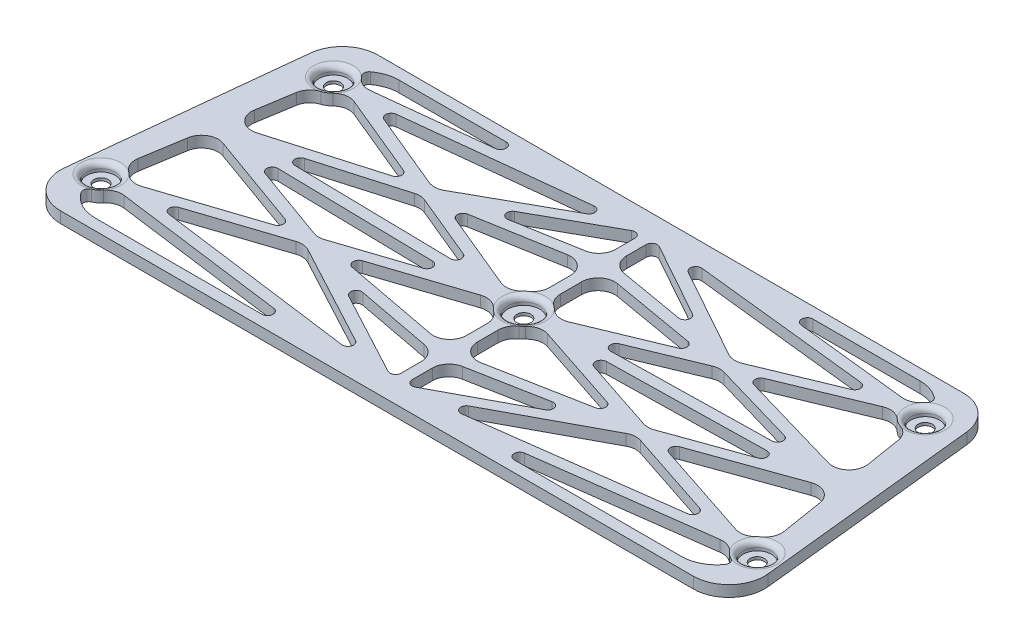
SolidWorks part; units mm, degrees
ref_plane "Front Plane" through (0, 0, 0) normal (0, 0, 1) x (1, 0, 0)
ref_plane "Top Plane" through (0, 0, 0) normal (0, 1, 0) x (1, 0, 0)
ref_plane "Right Plane" through (0, 0, 0) normal (1, 0, 0) x (0, 0, -1)
sketch "Sketch1" plane through (0, 0, 0) normal (0, 1, 0) x (1, 0, 0)
  line L0 (-101.6, -41.91) -> (-92.71, 41.91)
  line L1 (-101.6, -41.91) -> (101.6, -41.91)
  line L2 (-101.6, -41.91) -> (-101.6, 41.91)
  line L3 (-101.6, 41.91) -> (101.6, 41.91)
  line L4 (101.6, -41.91) -> (101.6, 41.91)
  line L5 (-101.6, -41.91) -> (101.6, 41.91) construction
  line L6 (-101.6, 41.91) -> (101.6, -41.91) construction
  line L7 (0, 41.91) -> (0, -41.91) construction
  line L8 (101.6, -41.91) -> (92.71, 41.91)
  circle A0 centre (0, 0) radius 2.032
  circle A1 centre (-93.6752, -27.0205) radius 2.032
  circle A2 centre (-84.4677, 30.1295) radius 2.032
  circle A3 centre (93.6752, -27.0205) radius 2.032
  circle A4 centre (84.4677, 30.1295) radius 2.032
  point P0 (0, 0)
  dimension "D1" = 4.064
  dimension "D6" = 4.064
  dimension "D2" = 203.2
  dimension "D3" = 83.82
  dimension "D4" = 8.89
  dimension "D5" = 83.946
  dimension "D7" = 14.8895
  dimension "D8" = 7.9248
  dimension "D9" = 57.15
  dimension "D10" = 9.2075
extrude "platw" add sketch "Sketch1" along normal blind 3.175 contours L1 L8 L3 L0 A3 A2 A1 A0 A4 region at (-94.9692, 0, 0.2318)
fillet "Fillet1" radius 10.16 2 edges at (101.6, 1.5875, 41.91) (-101.6, 1.5875, 41.91)
fillet "Fillet2" radius 10.16 2 edges at (-92.71, 1.5875, -41.91) (92.71, 1.5875, -41.91)
sketch "Sketch2" plane through (0, 3.175, 0) normal (0, 1, 0) x (1, 0, 0)
  circle A0 centre (-84.4677, 30.1295) radius 4.064
  circle A1 centre (-93.6752, -27.0205) radius 4.064
  circle A2 centre (93.6752, -27.0205) radius 4.064
  circle A3 centre (84.4677, 30.1295) radius 4.064
  circle A4 centre (0, 0) radius 4.572
  dimension "D1" = 8.128
  dimension "D2" = 9.144
extrude "countersinks" cut sketch "Sketch2" against normal blind 2.3813
sketch "Sketch3" plane through (0, 3.175, 0) normal (0, 1, 0) x (1, 0, 0)
  line L0 (-88.0237, -27.0205) -> (-6.1595, 0) construction
  line L1 (-47.0916, -13.5103) -> (-89.0714, 1.5545) construction
  line L2 (-88.0237, -27.0205) -> (0, -38.735) construction
  line L3 (-47.0916, -13.5103) -> (0, -22.4472) construction
  line L4 (-84.4677, 30.1295) -> (-93.6752, -27.0205)
  line L5 (-83.697, -38.735) -> (83.697, -38.735)
  line L6 (93.6752, -27.0205) -> (84.4677, 30.1295)
  line L7 (-74.3648, 38.735) -> (74.3648, 38.735)
  line L8 (-90.3054, -41.91) -> (90.3054, -41.91) construction
  line L9 (-83.5706, 41.91) -> (83.5706, 41.91) construction
  line L10 (-78.8162, 30.1295) -> (-6.1595, 0) construction
  line L11 (-47.0916, -13.5103) -> (0, -38.735) construction
  line L12 (-89.3283, -0.04) -> (-51.9664, -13.4475)
  line L13 (0, -38.735) -> (0, -6.1595)
  line L14 (0, 6.1595) -> (0, 38.735)
  line L15 (-78.8162, 30.1295) -> (0, 38.735) construction
  line L16 (0, 22.4473) -> (-42.4878, 15.0647) construction
  line L17 (-42.4878, 15.0647) -> (0, 38.735) construction
  line L18 (-6.1595, 0) -> (-89.0714, 1.5545) construction
  line L19 (-89.0714, 1.5545) -> (-42.4878, 15.0647) construction
  line L20 (-51.9664, -13.4475) -> (-88.2537, -25.4247)
  line L21 (-79.4439, -0.2138) -> (-47.07, -11.8314)
  line L22 (-47.07, -11.8314) -> (-15.5041, -1.4126)
  line L23 (-15.5041, -1.4126) -> (-79.4439, -0.2138)
  line L24 (-40.7674, -13.0946) -> (-5.9476, -1.6018)
  line L25 (-40.7674, -13.0946) -> (-1.5875, -20.5301)
  line L26 (-1.5875, -20.5301) -> (-1.5875, -5.9514)
  line L27 (-80.9563, -26.3596) -> (-8.4517, -36.0087)
  line L28 (-8.4517, -36.0087) -> (-47.2408, -15.2312)
  line L29 (-47.2408, -15.2312) -> (-80.9563, -26.3596)
  line L30 (-12.0338, -38.735) -> (-88.2467, -28.5923)
  line L31 (-37.213, -17.0008) -> (-1.5875, -36.0837)
  line L32 (-1.5875, -36.0837) -> (-1.5875, -23.7618)
  line L33 (-1.5875, -23.7618) -> (-37.213, -17.0008)
  line L34 (-79.0394, 31.702) -> (-14.626, 38.735)
  line L35 (-72.4873, 29.2236) -> (-7.6222, 36.3058)
  line L36 (-7.6222, 36.3058) -> (-42.5894, 16.8254)
  line L37 (-42.5894, 16.8254) -> (-72.4873, 29.2236)
  line L38 (-79.0534, 28.5093) -> (-47.2721, 15.3301)
  line L39 (-47.2721, 15.3301) -> (-88.7921, 3.2884)
  line L40 (-78.576, 2.9455) -> (-42.581, 13.3848)
  line L41 (-42.581, 13.3848) -> (-14.5103, 1.7443)
  line L42 (-14.5103, 1.7443) -> (-78.576, 2.9455)
  line L46 (0, 41.91) -> (0, -41.91) construction
  line L60 (-5.9405, 1.6278) -> (-36.829, 14.4367)
  line L61 (-36.829, 14.4367) -> (-1.5875, 20.5601)
  line L62 (-1.5875, 20.5601) -> (-1.5875, 5.9514)
  line L63 (-33.5443, 18.23) -> (-1.5875, 23.7827)
  line L64 (-1.5875, 23.7827) -> (-1.5875, 36.0334)
  line L65 (-1.5875, 36.0334) -> (-33.5443, 18.23)
  arc A0 (-79.0394, 31.702) -> (-82.063, 35.2439) centre (-84.4677, 30.1295) ccw
  arc A1 (-85.3666, 24.5499) -> (-79.0534, 28.5093) centre (-84.4677, 30.1295) ccw
  arc A4 (-84.4677, 30.1295) -> (-74.3648, 38.735) centre (-74.3648, 28.5018) cw
  arc A5 (74.3648, 38.735) -> (84.4677, 30.1295) centre (74.3648, 28.5018) cw
  arc A6 (-93.6752, -27.0205) -> (-83.697, -38.735) centre (-83.697, -28.6281) ccw
  arc A7 (83.697, -38.735) -> (93.6752, -27.0205) centre (83.697, -28.6281) ccw
  arc A9 (-92.7763, -21.441) -> (-88.2467, -28.5923) centre (-93.6752, -27.0205) cw
  arc A10 (-88.2467, -28.5923) -> (-92.9783, -32.6289) centre (-93.6752, -27.0205) cw
  circle A13 centre (0, 0) radius 6.1595
  point P73 (-1.5875, -13.2408)
  dimension "D3" = 12.319
  dimension "D4" = 5.6515
  dimension "D5" = 5.6515
  dimension "D1" = 3.175
  dimension "D2" = 3.175
extrude "pocket 1" cut sketch "Sketch3" against normal through all contours A4 L34 L7 | L37 L36 L35 | L64 L65 L63 | L42 L41 L40 | L39 L38 L4 | L62 L61 L60 | L22 L23 L21 | L20 L12 L4 | L28 L29 L27 | L32 L33 L31 | L25 L26 L24 | A6 L5 L30 region at (-73.0435, 3.175, -15.9243) region at (-58.1721, 3.175, -36.3358) region at (-77.871, 3.175, 13.1847) region at (-64.1002, 3.175, 35.2582) region at (-13.8195, 3.175, -12.03) region at (-15.1255, 3.175, 11.6139) region at (-47.3393, 3.175, 4.4859) region at (-45.5496, 3.175, 25.8665) region at (-13.4627, 3.175, 25.6155) region at (-40.8996, 3.175, -27.4516) region at (-45.2224, 3.175, -6.0249) region at (-12.2398, 3.175, -26.0154)
fillet "acute angles" radius 1.5875 20 edges at (-1.5875, 1.5875, -36.0334) (-33.5443, 1.5875, -18.23) (-14.626, 1.5875, -38.735) (-7.6222, 1.5875, -36.3058) (-72.4873, 1.5875, -29.2236) (-47.2721, 1.5875, -15.3301) (-36.829, 1.5875, -14.4367) (-14.5103, 1.5875, -1.7443) (-78.576, 1.5875, -2.9455) (-12.0338, 1.5875, 38.735) (-8.4517, 1.5875, 36.0087) (-1.5875, 1.5875, 36.0837) (-37.213, 1.5875, 17.0008) (-51.9664, 1.5875, 13.4475) (-40.7674, 1.5875, 13.0946) (-15.5041, 1.5875, 1.4126) (-79.4439, 1.5875, 0.2138) (-80.9563, 1.5875, 26.3596) (-92.9783, 1.5875, 32.6289) (-82.063, 1.5875, -35.2439)
fillet "Fillet5" radius 4.7625 20 edges at (-1.5875, 1.5875, -20.5601) (-1.5875, 1.5875, -23.7827) (-42.5894, 1.5875, -16.8254) (-42.581, 1.5875, -13.3848) (-88.7921, 1.5875, -3.2884) (-1.5875, 1.5875, 23.7618) (-1.5875, 1.5875, 20.5301) (-47.2408, 1.5875, 15.2312) (-47.07, 1.5875, 11.8314) (-89.3283, 1.5875, 0.04) (-1.5875, 1.5875, 5.9514) (-5.9476, 1.5875, 1.6018) (-88.2467, 1.5875, 28.5923) (-88.2537, 1.5875, 25.4247) (-92.7763, 1.5875, 21.441) (-5.9405, 1.5875, -1.6278) (-1.5875, 1.5875, -5.9514) (-85.3666, 1.5875, -24.5499) (-79.0534, 1.5875, -28.5093) (-79.0394, 1.5875, -31.702)
ref_plane "Plane1" through (0, 0, 0) normal (-1, 0, 0) x (0, 0, 1)
mirror "Mirror1" about plane through (0, 0, 0) normal (-1, 0, 0) of "Fillet5", "acute angles", "pocket 1"
fillet "Fillet6" radius 1.5875 5 edges at (84.4677, 3.175, -26.0655) (93.6752, 3.175, 31.0845) (-93.6752, 3.175, 31.0845) (-84.4677, 3.175, -26.0655) (0, 3.175, 4.572)
equation "\"q1\"= .0625"
